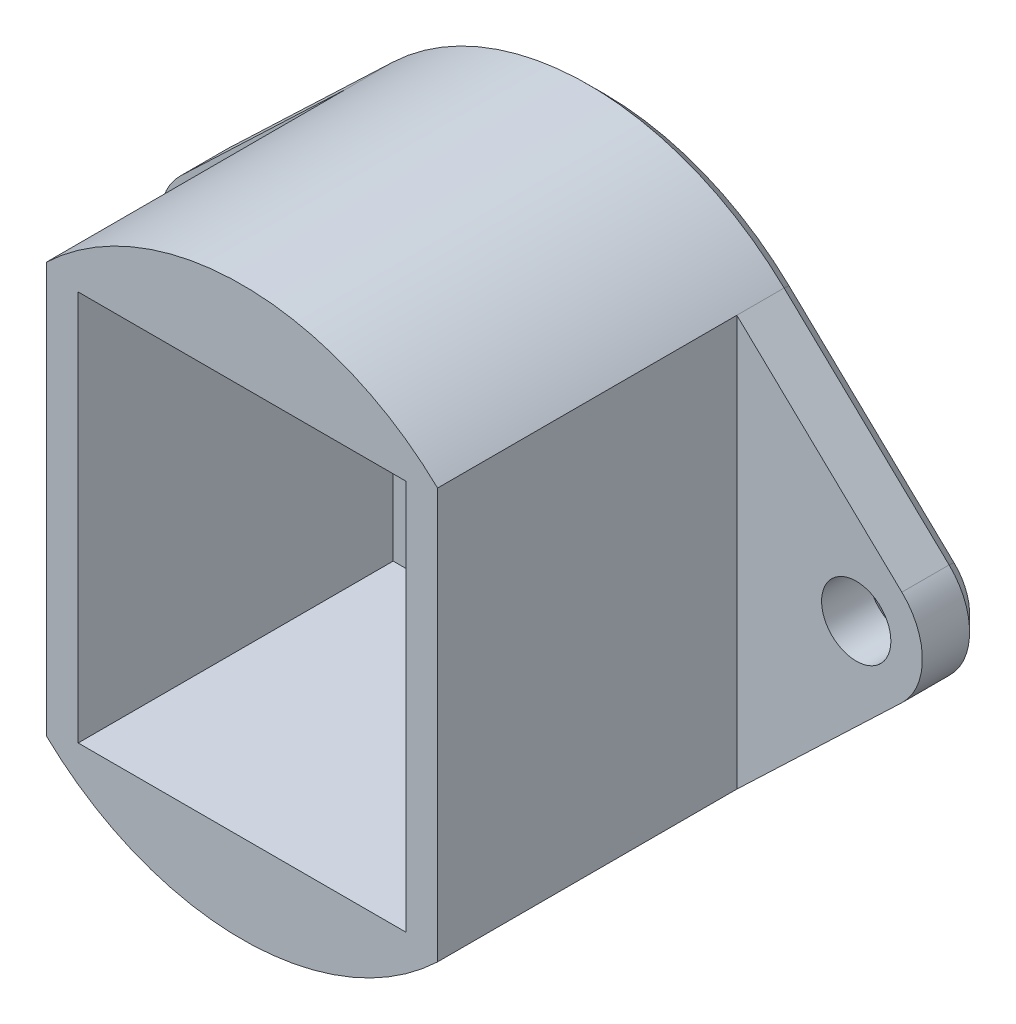
SolidWorks part; units mm, degrees
material "ABS"
ref_plane "Front" through (0, 0, 0) normal (0, 0, 1) x (1, 0, 0)
ref_plane "Top" through (0, 0, 0) normal (0, 1, 0) x (1, 0, 0)
ref_plane "Right" through (0, 0, 0) normal (1, 0, 0) x (0, 0, -1)
sketch "Эскиз2" plane through (0, 0, 0) normal (0, 0, 1) x (1, 0, 0)
  line L0 (6.21, 6.5143) -> (11.449, 1.52)
  line L1 (11.449, -1.52) -> (6.21, -6.5143)
  line L2 (-10, 0) -> (10, 0) construction
  line L3 (-6.21, -6.5143) -> (-11.449, -1.52)
  line L4 (-6.21, 6.5143) -> (-11.449, 1.52)
  line L5 (0, -9) -> (0, 9) construction
  arc A1 (11.449, 1.52) -> (11.449, -1.52) centre (10, 0) cw
  circle A2 centre (10, 0) radius 1.1
  arc A3 (6.21, -6.5143) -> (-6.21, -6.5143) centre (0, 0) cw
  circle A4 centre (-10, 0) radius 1.1
  arc A5 (-11.449, -1.52) -> (-11.449, 1.52) centre (-10, 0) cw
  arc A6 (6.21, 6.5143) -> (-6.21, 6.5143) centre (0, 0) ccw
  circle A7 centre (0, 4.5) radius 1
  circle A9 centre (0, -4.5) radius 1
  circle A10 centre (0, 0) radius 1.7
  point P12 (0, 0)
  dimension "D1" = 2.2
  dimension "D2" = 2.1
  dimension "D4" = 18
  dimension "D5" = 2
  dimension "D7" = 3.4
  dimension "D3" = 20
  dimension "D6" = 9
extrude "Бобышка-Вытянуть1" add sketch "Эскиз2" along normal blind 2
sketch "Эскиз3" plane through (0, 0, 2) normal (0, 0, 1) x (1, 0, 0)
  line L0 (-6.21, 6.5143) -> (-11.449, 1.52) construction
  line L1 (6.21, 6.5143) -> (6.21, -6.5143)
  line L2 (5.2, 6.2) -> (-5.2, 6.2)
  line L3 (5.2, 6.2) -> (5.2, -6.2)
  line L4 (5.2, -6.2) -> (-5.2, -6.2)
  line L5 (-5.2, 6.2) -> (-5.2, -6.2)
  line L6 (5.2, 6.2) -> (-5.2, -6.2) construction
  line L7 (5.2, -6.2) -> (-5.2, 6.2) construction
  line L8 (-6.21, -6.5143) -> (-6.21, 6.5143)
  arc A2 (6.21, -6.5143) -> (-6.21, -6.5143) centre (0, 0) cw
  arc A3 (-6.21, -6.5143) -> (6.21, -6.5143) centre (0, 0) ccw construction
  arc A4 (6.21, 6.5143) -> (-6.21, 6.5143) centre (0, 0) ccw
  circle A5 centre (0, 0) radius 8.092 construction
  dimension "D1" = 12.4
  dimension "D3" = 0.908
  dimension "D2" = 10.4
extrude "Бобышка-Вытянуть2" add sketch "Эскиз3" along normal offset from surface (9.5 mm away) 11.5 up to face at (0, 0, 0)
sketch "Эскиз4" plane through (0, 0, 2) normal (0, 0, 1) x (1, 0, 0)
  line L0 (5.2, -6.2) -> (5.2, 6.2) construction
  line L1 (-5.2, -6.2) -> (5.2, -6.2)
  line L2 (-5.2, -6.2) -> (-5.2, 6.2)
  line L3 (-5.2, 6.2) -> (5.2, 6.2)
  line L4 (5.2, -6.2) -> (5.2, 6.2)
  line L5 (-5.2, -6.2) -> (5.2, 6.2) construction
  line L6 (-5.2, 6.2) -> (5.2, -6.2) construction
  point P0 (0, 0)
extrude "Вырез-Вытянуть1" cut sketch "Эскиз4" against normal blind 0.5
sketch "Эскиз5" plane through (0, 0, 1.5) normal (0, 0, 1) x (1, 0, 0)
  circle A0 centre (0, 0) radius 2.25
  dimension "D1" = 4.5
extrude "Вырез-Вытянуть2" cut sketch "Эскиз5" against normal blind 0.9
chamfer "Фаска1" distance 0.5 angle 45 13 edges at (-8.9, 0, 0) (1.7, 0, 0) (-1, -4.5, 0) (1, 4.5, 0) (11.1, 0, 0) (-8.8295, 4.0171, 0) (-12.1, 0, 0) (-8.8295, -4.0171, 0) (8.8295, -4.0171, 0) (12.1, 0, 0) (8.8295, 4.0171, 0) (0, -9, 0) (0, 9, 0)
